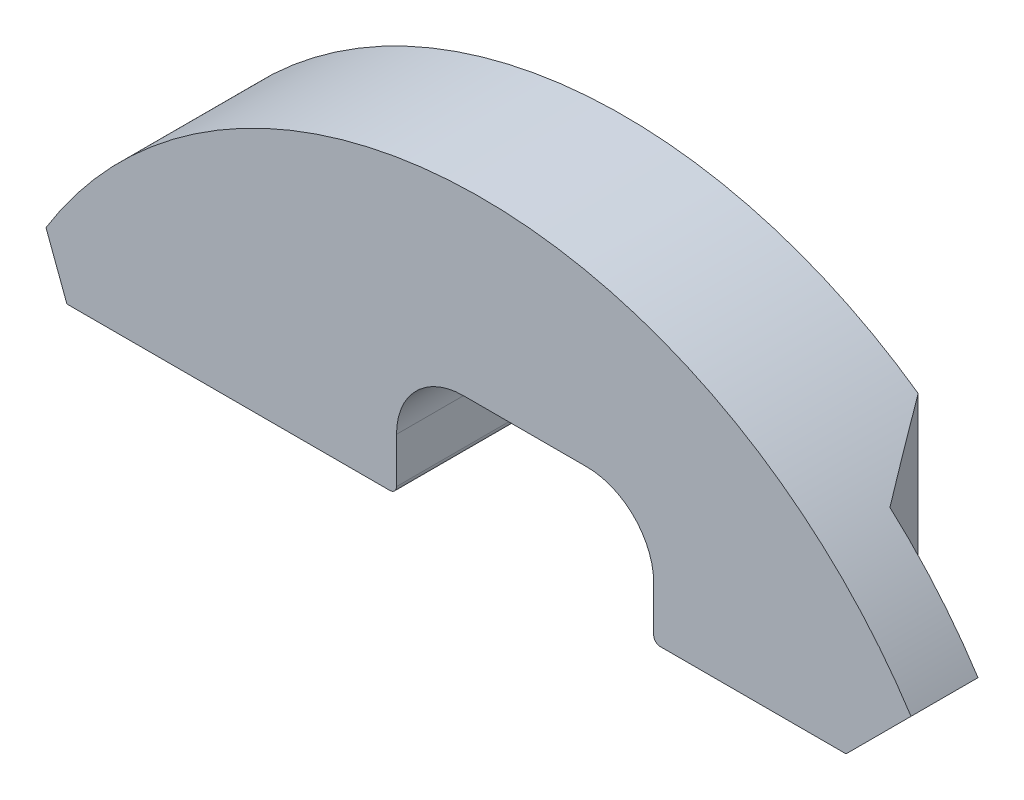
SolidWorks part; units mm, degrees
material "Polyurethane Foam Rigid"
ref_plane "Front Plane" through (0, 0, 0) normal (0, 0, 1) x (1, 0, 0)
ref_plane "Top Plane" through (0, 0, 0) normal (0, 1, 0) x (1, 0, 0)
ref_plane "Right Plane" through (0, 0, 0) normal (1, 0, 0) x (0, 0, -1)
sketch "Sketch1" plane through (0, 0, 0) normal (0, 0, 1) x (1, 0, 0)
  point P0 (0, 45.106)
  line B0 (-48.768, 0) -> (-48.768, 45.106)
  line B1 (-48.768, 45.106) -> (48.768, 45.106)
  line B2 (48.768, 0) -> (48.768, 45.106)
  line B3 (-48.768, 0) -> (-192.96, 0)
  line B4 (48.768, 0) -> (159.8172, 0)
  arc B5 (-192.96, 0) -> (159.8172, 0) centre (-16.5714, -80.3119) cw
sketch_block_instance "splash_guards-1"
sketch_block "splash_guards"
extrude "Boss-Extrude1" add sketch "Sketch1" along normal blind 53.975
fillet "Fillet1" radius 25.4 2 edges at (48.768, 45.106, 26.9875) (-48.768, 45.106, 26.9875)
fillet "Fillet2" radius 2.54 2 edges at (-48.768, 0, 26.9875) (48.768, 0, 26.9875)
chamfer "Chamfer1" distance 38.1 angle 45 1 edges at (159.8172, 0, 26.9875) first distance on face at (105.5626, 0, 26.9875)
chamfer "Chamfer2" distance 25.4 angle 45 1 edges at (-192.96, 0, 26.9875) first distance on face at (-26.955, 62.6564, 26.9875)
sketch "Sketch2" plane through (0, 0, 0) normal (0, 1, 0) x (1, 0, 0)
  line L6 (163.7686, -28.575) -> (112.9686, -28.575) construction
  line L7 (112.9686, -28.575) -> (49.4686, 73.025) construction
  line L8 (163.7686, -28.575) -> (112.9686, -28.575)
  line L9 (112.9686, -28.575) -> (49.4686, 73.025)
  line L10 (49.4686, 73.025) -> (163.7686, 73.025)
  line L11 (163.7686, 73.025) -> (163.7686, -28.575)
extrude "Cut-Extrude2" cut sketch "Sketch2" along normal through all
